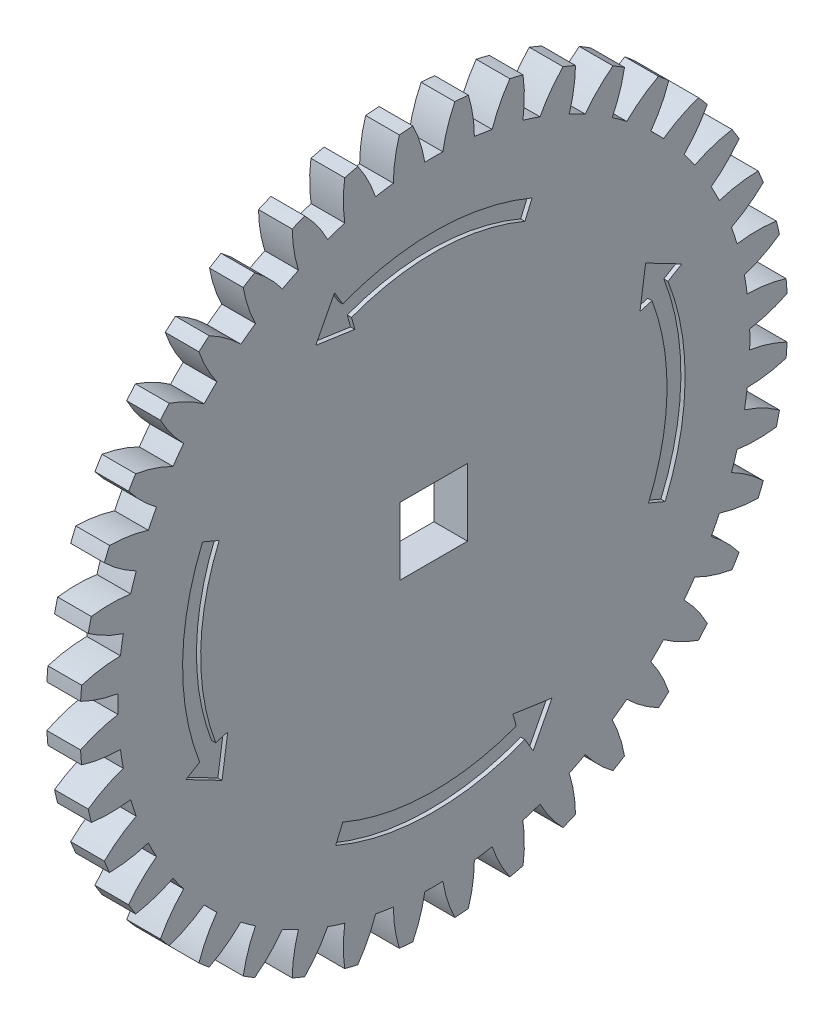
SolidWorks part; units mm, degrees
ref_plane "Plane1" through (0, 0, 0) normal (0, 0, 1) x (1, 0, 0)
ref_plane "Plane2" through (0, 0, 0) normal (0, 1, 0) x (1, 0, 0)
ref_plane "Plane3" through (0, 0, 0) normal (1, 0, 0) x (0, 0, -1)
other "Configuration Table"
sketch "HoldingSke" plane through (0, 0, 0) normal (0, 1, 0) x (1, 0, 0)
  line L0 (0, 0) -> (0.383, -0.3214)
  line L1 (-15, 0) -> (100, 0) construction
  line L2 (0, 0) -> (-2.1039, 2.3779)
  line L3 (0, 0) -> (-11.863, 4.5341)
  line L4 (0, 0) -> (6.6156, 5.5511)
  line L5 (0, 0) -> (-46.8476, -17.4728)
  line L6 (0, 0) -> (-3.3159, -2.2372)
  line L7 (-2.1039, 2.3779) -> (8.6587, 51.2066)
  line L8 (-76.2, 54.61) -> (-76.1, 54.61)
  line L9 (-67.7845, 28.3722) -> (-49.3413, 33.142)
  line L10 (-76.2, 71.12) -> (104.1128, 71.12)
  line L11 (0, 0) -> (-4, 0)
  line L12 (-76.2, 101.6) -> (-76.133, 101.6)
  line L13 (24.9733, 27.94) -> (52.9518, 28.4284)
  line L14 (24.9733, 27.94) -> (24.9743, 27.94)
  line L15 (24.9733, 27.94) -> (100.4006, 29.5858)
  line L16 (-63.627, -2) -> (-12.827, -2)
  circle A0 centre (0, 0) radius 0.4
  circle A1 centre (0, 0) radius 37.499
  circle A2 centre (0, 0) radius 37.5
  circle A3 centre (0, 0) radius 0.4
  dimension "MHD" = 74.998
  dimension "Hub_dia" = 75
  dimension "Bore" = 0.8
  dimension "MBD" = 0.8
  dimension "Num_teeth" = 40
  dimension "Pitch" = 0.5
  dimension "Overall_len" = 50
  dimension "Show_teeth" = 40
  dimension "Thickness" = 4
  dimension "OAL" = 50.0008
  dimension "T_dim" = 0.1
  dimension "Ap" = 14.5
  dimension "H" = 19.05
  dimension "Pitch_radius" = 180.3128
  dimension "Width" = 4
  dimension "Backlash" = 0.067
  dimension "Addendum_fac" = 1
  dimension "Dedendum_fac" = 1.25
  dimension "Clearance_fac" = 0.25
  dimension "Dedendum_add" = 0.001
  dimension "Module" = 2
sketch "BasProSke" plane through (0, 0, 0) normal (0, 1, 0) x (1, 0, 0)
  line L0 (-10, 0) -> (60, 0) construction
  line L1 (0, 0) -> (0, 42)
  line L2 (0, 0) -> (4, 0)
  line L3 (4, 0) -> (4, 42)
  line L4 (4, 42) -> (0, 42)
  dimension "Thickness" = 4
  dimension "Diameter" = 84
revolve "Base-Revolve" add sketch "BasProSke" angle 360 about L0
sketch "TooCutSke" plane through (0, 0, 0) normal (1, 0, 0) x (0, 0, -1)
  line L1 (0, 0) -> (0, 107) construction
  line L2 (0, 0) -> (-1.6876, 39.9644) construction
  line L3 (0, 0) -> (-6.2726, 79.7007) construction
  line L4 (-1.6876, 39.9644) -> (-3.1363, 39.8504) construction
  arc A0 (1.0692, 37.4838) -> (-1.0692, 37.4838) centre (0, 0) ccw
  arc A1 (2.5075, 41.9505) -> (-2.5075, 41.9505) centre (0, 0) ccw
  circle A2 centre (0, 0) radius 40 construction
  circle A3 centre (0, 0) radius 38.7259 construction
  arc A4 (-1.0692, 37.4838) -> (-2.5075, 41.9505) centre (-16.8537, 34.8662) ccw
  arc A5 (2.5075, 41.9505) -> (1.0692, 37.4838) centre (16.8537, 34.8662) ccw
  dimension "Root_dia" = 74.998
  dimension "Overcut_dia" = 84.0508
  dimension "Pitch_dia" = 80
  dimension "Base_dia" = 77.4518
  dimension "Flank_rad" = 16
  dimension "Half_ang" = 4.5
  dimension "Half_CT" = 1.4531
extrude "ToothCut" cut sketch "TooCutSke" along normal through all
fillet "Breaks" [suppressed] radius 0.04 tangent propagation no
fillet "RootFillets" [suppressed] radius 0.501
pattern_circular "TeethCuts" count 40 every 9 about axis through (-10, 0, 0) along (1, 0, 0) of "ToothCut", "RootFillets", "Breaks"
sketch "HubNeaOneSke" plane through (0, 0, 0) normal (-1, 0, 0) x (0, 0, 1)
  circle A0 centre (0, 0) radius 37.499
  dimension "Diameter" = 74.998
extrude "HubNearOne" [suppressed] add sketch "HubNeaOneSke" along normal blind 46.0008
sketch "HubNeaBotSke" plane through (0, 0, 0) normal (-1, 0, 0) x (0, 0, 1)
  circle A0 centre (0, 0) radius 37.499
  dimension "Diameter" = 74.998
extrude "HubNearBoth" [suppressed] add sketch "HubNeaBotSke" along normal blind 23.0004
ref_plane "FarPln" through (4, 0, 0) normal (1, 0, 0) x (0, 0, -1)
sketch "HubFarSke" plane through (4, 0, 0) normal (1, 0, 0) x (0, 0, -1)
  circle A0 centre (0, 0) radius 37.499
  dimension "Diameter" = 74.998
extrude "HubFar" [suppressed] add sketch "HubFarSke" along normal blind 23.0004
sketch "KeySke" plane through (0, 0, 0) normal (1, 0, 0) x (0, 0, -1)
  line L0 (-0.05, 0) -> (-0.05, 0.5)
  line L1 (-0.05, 0.5) -> (0.05, 0.5)
  line L2 (0.05, 0.5) -> (0.05, 0)
  line L3 (0, 0) -> (0, 34) construction
  line L4 (-0.05, 0) -> (0.05, 0)
  dimension "Offset" = 0.5
  dimension "Width" = 0.1
extrude "Keyway" [suppressed] cut sketch "KeySke" along normal mid plane 100.0015
pattern_circular "Keyway2" [suppressed] count 2 every 90 about axis through (-10, 0, 0) along (1, 0, 0)
sketch "草图1" plane through (4, 0, 0) normal (1, 0, 0) x (0, 0, -1)
  line L1 (-4, 4) -> (4, 4)
  line L2 (-4, 4) -> (-4, -4)
  line L3 (-4, -4) -> (4, -4)
  line L4 (4, 4) -> (4, -4)
  line L5 (-4, 4) -> (4, -4) construction
  line L6 (-4, -4) -> (4, 4) construction
  point P0 (0, 0)
  dimension "D1" = 8
  dimension "D2" = 8
extrude "切除-拉伸1" cut sketch "草图1" against normal through all
ref_axis "Axis1" through (80.9, 0, 0) along (-1, 0, 0)
sketch "Sketch1" plane through (4, 0, 0) normal (1, 0, 0) x (0, 0, -1)
  line L0 (27.4499, -11.651) -> (25.4731, -10.8119)
  line L1 (0, 0) -> (25.4731, -10.8119) construction
  line L2 (27.7911, 10.8119) -> (29.4297, 11.7857)
  line L3 (29.4297, 11.7857) -> (25.1342, 14.0188)
  line L4 (25.1342, 14.0188) -> (24.4617, 9.3828)
  line L5 (24.4617, 9.3828) -> (25.8886, 9.7755)
  circle A0 centre (0, 0) radius 29.8202 construction
  arc A1 (27.4499, -11.651) -> (27.7911, 10.8119) centre (0, 0) ccw
  arc A2 (25.8886, 9.7755) -> (25.4731, -10.8119) centre (0, 0) cw
extrude "Cut-Extrude1" cut sketch "Sketch1" against normal blind 0.5
pattern_circular "CirPattern1" count 4 over 360 about axis through (80.9, 0, 0) along (-1, 0, 0) of "Cut-Extrude1"
equation "' \"Module@HoldingSke\" = 6.35"
equation "' \"Num_teeth@HoldingSke\" = 12"
equation "' \"Ap@HoldingSke\" =  20"
equation "' \"Ap@HoldingSke\" = 20"
equation "' \"Width@HoldingSke\" = 0.5 * 25.4"
equation "' \"Hub_dia@HoldingSke\"= 1 * 25.4"
equation "' \"Hub_dia@HoldingSke\" = 1 * 25.4"
equation "' \"Overall_len@HoldingSke\" = 1.0 * 25.4"
equation "' \"Bore@HoldingSke\" = 0.75 * 25.4"
equation "' \"T_dim@HoldingSke\" = 0.1 * 25.4"
equation "' \"Width@KeySke\" = 0.25 * 25.4"
equation "' \"Show_teeth@HoldingSke\" = 13"
equation "' \"Backlash@HoldingSke\" = 0.009 * 25.4"
equation "' \"Addendum_fac@HoldingSke\" = 1.0"
equation "' \"Dedendum_fac@HoldingSke\" = 1.25"
equation "' \"Dedendum_add@HoldingSke\" = 0.00005 * 25.4"
equation "' \"Clearance_fac@HoldingSke\" = 0.25"
equation "\"Pitch@HoldingSke\" = 1 / \"Module@HoldingSke\""
equation "\"Overcut_dia@TooCutSke\" = (\"Num_teeth@HoldingSke\" + 2 * \"Addendum_fac@HoldingSke\") / \"Pitch@HoldingSke\" + 0.002 * 25.4"
equation "\"Pitch_dia@TooCutSke\" = \"Num_teeth@HoldingSke\" / \"Pitch@HoldingSke\""
equation "\"Base_dia@TooCutSke\" = \"Num_teeth@HoldingSke\" / \"Pitch@HoldingSke\" * cos((\"Ap@HoldingSke\"  * 3.14159265 / 180))"
equation "\"Root_dia@TooCutSke\" = (\"Num_teeth@HoldingSke\" + 2) / \"Pitch@HoldingSke\" - 2 * (\"Addendum_fac@HoldingSke\" + \"Dedendum_fac@HoldingSke\") / \"Pitch@HoldingSke\" - \"Dedendum_add@HoldingSke\" * 2"
equation "\"Half_ang@TooCutSke\" = 180 / \"Num_teeth@HoldingSke\""
equation "\"Half_CT@TooCutSke\" = \"Num_teeth@HoldingSke\" / \"Pitch@HoldingSke\" * sin((3.14159265 / 2 / \"Num_teeth@HoldingSke\")) / 2 - 7 * \"Backlash@HoldingSke\" / 4"
equation "\"Flank_rad@TooCutSke\" = \"Num_teeth@HoldingSke\" / \"Pitch@HoldingSke\" / 5"
equation "\"Radius@RootFillets\" = \"Clearance_fac@HoldingSke\" / \"Pitch@HoldingSke\" + \"Dedendum_add@HoldingSke\""
equation "\"Break_rad@Breaks\" = 0.02 / \"Pitch@HoldingSke\""
equation "\"Thickness@HoldingSke\" = \"Width@HoldingSke\""
equation "\"OAL@HoldingSke\" = \"Thickness@HoldingSke\""
equation "\"MHD@HoldingSke\" = (\"Num_teeth@HoldingSke\" + 2) / \"Pitch@HoldingSke\" - 2 * (\"Addendum_fac@HoldingSke\" + \"Dedendum_fac@HoldingSke\")  / \"Pitch@HoldingSke\" - \"Dedendum_add@HoldingSke\" * 2"
equation "\"MBD@HoldingSke\" = (\"Num_teeth@HoldingSke\" + 2) / \"Pitch@HoldingSke\" - 2 * (\"Addendum_fac@HoldingSke\" + \"Dedendum_fac@HoldingSke\")  / \"Pitch@HoldingSke\" - \"Dedendum_add@HoldingSke\" * 2 - 0.002 * 25.4"
equation "\"MHD@HoldingSke\" = ((sgn( \"MHD@HoldingSke\" - \"Hub_dia@HoldingSke\" )-1)*( \"MHD@HoldingSke\" - \"Hub_dia@HoldingSke\" ))/-2+ \"Hub_dia@HoldingSke\""
equation "\"MBD@HoldingSke\" = ((sgn( \"MBD@HoldingSke\" - \"Bore@HoldingSke\" )-1)*( \"MBD@HoldingSke\" - \"Bore@HoldingSke\" ))/-2+ \"Bore@HoldingSke\""
equation "\"OAL@HoldingSke\" = ((sgn( \"OAL@HoldingSke\" - \"Overall_len@HoldingSke\" )+1)*( \"OAL@HoldingSke\" - \"Overall_len@HoldingSke\" ))/2 + \"Overall_len@HoldingSke\" + 0.000002 * 25.4"
equation "\"Num_teeth@TeethCuts\" = int( \"Show_teeth@HoldingSke\" ) + 1"
equation "\"Num_teeth@TeethCuts\" = ((sgn( \"Num_teeth@TeethCuts\" - \"Num_teeth@HoldingSke\" )-1)*( \"Num_teeth@TeethCuts\" - \"Num_teeth@HoldingSke\" ))/-2+ \"Num_teeth@HoldingSke\""
equation "\"Num_teeth@TeethCuts\" = ((sgn( \"Num_teeth@TeethCuts\" - 2.0)+1)*( \"Num_teeth@TeethCuts\" - 2.0))/2 +2.0"
equation "\"Angle@TeethCuts\" = 360.0 / \"Num_teeth@HoldingSke\""
equation "\"Diameter@BasProSke\" = (\"Num_teeth@HoldingSke\" + 2 * \"Addendum_fac@HoldingSke\") / \"Pitch@HoldingSke\""
equation "\"Thickness@BasProSke\"  = \"Thickness@HoldingSke\""
equation "' \"Fillet_rad@BasProSke\" =  \"Thickness@HoldingSke\" * 0.05"
equation "' \"Fillet_rad@BasProSke\" = \"Thickness@HoldingSke\" * 0.05"
equation "\"MHD@HoldingSke\" = ((sgn( \"MHD@HoldingSke\" - \"Root_dia@TooCutSke\" )-1)*( \"MHD@HoldingSke\" - \"Root_dia@TooCutSke\" ))/-2+ \"Root_dia@TooCutSke\""
equation "\"Diameter@HubNeaOneSke\" = \"MHD@HoldingSke\""
equation "\"Length@HubNearOne\" = \"OAL@HoldingSke\" - \"Thickness@BasProSke\""
equation "\"Diameter@HubNeaBotSke\" = \"MHD@HoldingSke\""
equation "\"Length@HubNearBoth\" = ( \"OAL@HoldingSke\" - \"Thickness@BasProSke\" ) / 2.0"
equation "\"Thickness@FarPln\" = \"Thickness@BasProSke\""
equation "\"Diameter@HubFarSke\" = \"MHD@HoldingSke\""
equation "\"Length@HubFar\" = ( \"OAL@HoldingSke\" - \"Thickness@BasProSke\" ) / 2.0"
equation "\"D1@Keyway\" = \"OAL@HoldingSke\" * 2.0"
equation "\"Offset@KeySke\" = \"T_dim@HoldingSke\" + \"MBD@HoldingSke\" / 2.0"
